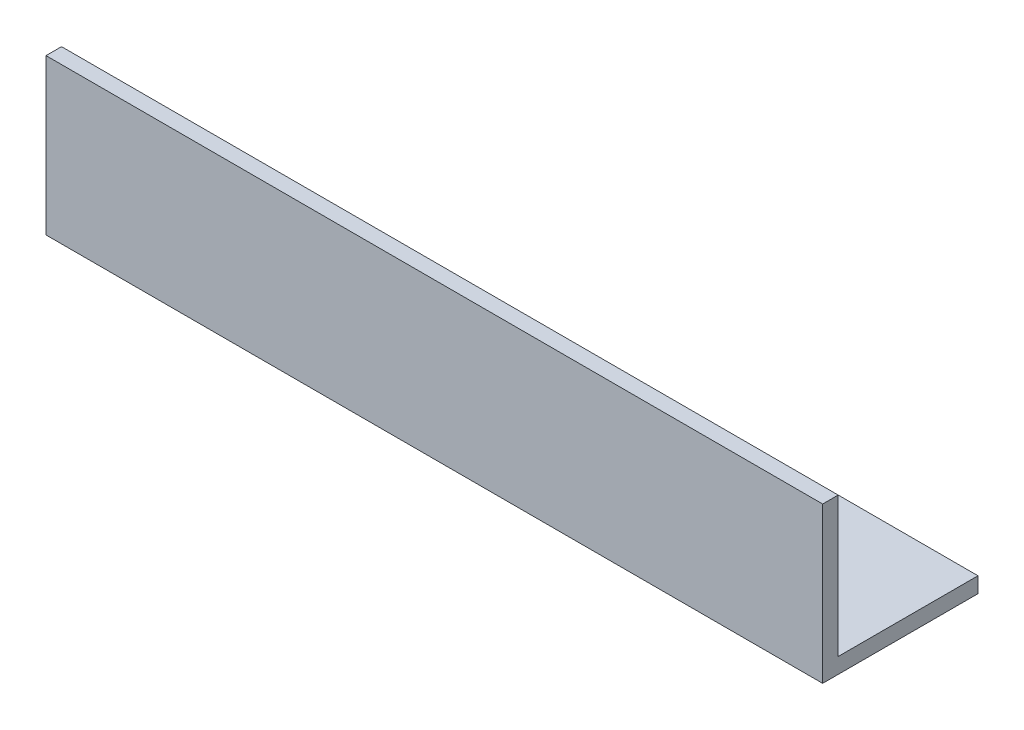
SolidWorks part; units mm, degrees
ref_plane "Спереди" through (0, 0, 0) normal (0, 0, 1) x (1, 0, 0)
ref_plane "Сверху" through (0, 0, 0) normal (0, 1, 0) x (1, 0, 0)
ref_plane "Справа" through (0, 0, 0) normal (1, 0, 0) x (0, 0, -1)
sketch "Эскиз1" plane through (0, 0, 0) normal (1, 0, 0) x (0, 0, -1)
  line L0 (0, 0) -> (0, 30)
  line L1 (0, 0) -> (30, 0)
extrude "Вытянуть-Тонкостенный1" add sketch "Эскиз1" along normal blind 150 thin thin type one direction reverse wall 3
